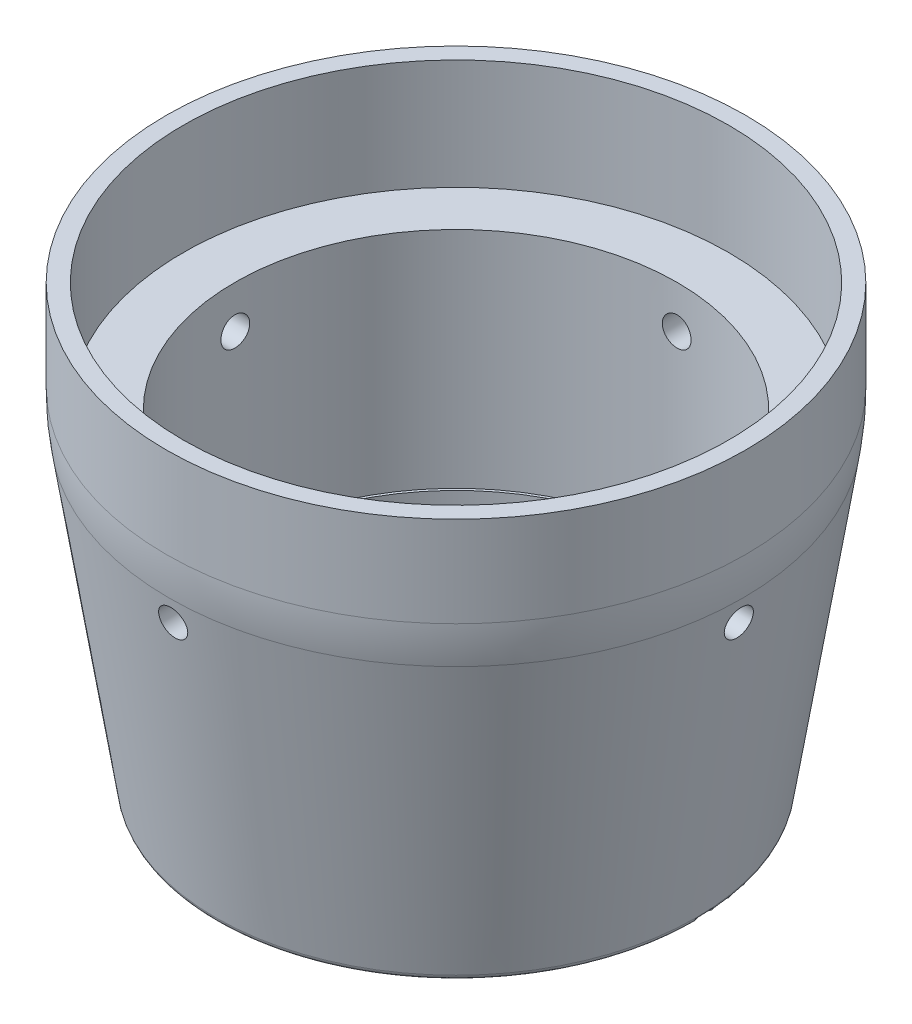
SolidWorks part; units mm, degrees
material "6061-T6 (SS)"
ref_plane "Front Plane" through (0, 0, 0) normal (0, 0, 1) x (1, 0, 0)
ref_plane "Top Plane" through (0, 0, 0) normal (0, 1, 0) x (1, 0, 0)
ref_plane "Right Plane" through (0, 0, 0) normal (1, 0, 0) x (0, 0, -1)
sketch "Sketch2" plane through (0, 0, 0) normal (0, 0, 1) x (1, 0, 0)
  line L8 (22.0472, -22.4282) -> (22.0472, -0.0762)
  line L10 (28.8925, 10.922) -> (28.8925, -0.0762)
  line L11 (28.8925, -0.0762) -> (23.8252, -32.512)
  line L12 (23.8252, -32.512) -> (21.7932, -32.512)
  line L13 (21.7932, -32.512) -> (21.7932, -22.4282)
  line L14 (22.0472, -0.0762) -> (27.1907, -0.0762)
  line L18 (21.7932, -22.4282) -> (22.0472, -22.4282)
  line L19 (27.1907, -0.0762) -> (27.1907, 10.922)
  line L20 (-28.8925, 10.922) -> (28.8925, 10.922) construction
  line L21 (27.1907, 10.922) -> (28.8925, 10.922)
  line L22 (21.717, -32.512) -> (21.717, -22.352) construction
  line L23 (21.971, -22.352) -> (21.971, 7.62) construction
  line L24 (-21.971, -22.352) -> (21.971, -22.352) construction
  line L25 (-27.1145, 0) -> (27.1145, 0) construction
  line L27 (27.1145, 0) -> (27.1145, 10.922) construction
  line L28 (-21.717, -32.512) -> (21.717, -32.512) construction
  dimension "D1" = 0.0762
  dimension "D2" = 0.0762
  dimension "D3" = 0.0762
  dimension "D4" = 0.0762
  dimension "D5" = 0.0762
  dimension "D6" = 2.032
ref_axis "Axis1" through (0, -34.5451, 0) along (0, 1, 0)
revolve "Revolve1" add sketch "Sketch2" angle 360 about axis through (0, -34.5451, 0) along (0, 1, 0)
ref_plane "Plane1" through (0, 0, 28.8925) normal (0, 0, 1) x (1, 0, 0)
sketch "Sketch3" plane through (0, 0, 28.8925) normal (0, 0, 1) x (1, 0, 0)
  line L0 (0, -34.5451) -> (0, 13.0871) construction
  line L2 (28.8925, 10.922) -> (-28.8925, 10.922) construction
  point P0 (0, -4.318)
  dimension "D1" = 15.24
hole_wizard "Tap Drill for #6-40 Tap1" positions "Sketch5" profile "Sketch7" hole size "#6-40" standard "ANSI Inch" end condition up to next
sketch "Sketch5" plane through (0, 0, 28.8925) normal (0, 0, 1) x (1, 0, 0)
  point P0 (0, -4.318)
sketch "Sketch7" plane through (0, -4.318, 28.8925) normal (1, 0, 0) x (0, -1, 0)
  line L0 (0, 0) -> (0, 6.8453)
  line L1 (0, 6.8453) -> (1.4351, 6.8453)
  line L2 (1.4351, 6.8453) -> (1.4351, 0)
  line L5 (1.4351, 0) -> (0, 0)
  line L11 (0, -6.35) -> (0, 107.95) construction
  dimension "Thru Hole Dia." = 2.8702
  dimension "Thru Hole Depth" = 6.8453
pattern_circular "CirPattern1" count 4 over 360 about axis through (0, -34.5451, 0) along (0, -1, 0) of "Tap Drill for #6-40 Tap1"
fillet "Fillet1" radius 0.635 1 edges at (0, -32.512, -23.8252)
fillet "Fillet2" radius 25.4 1 edges at (0, -0.0762, -28.8925)
